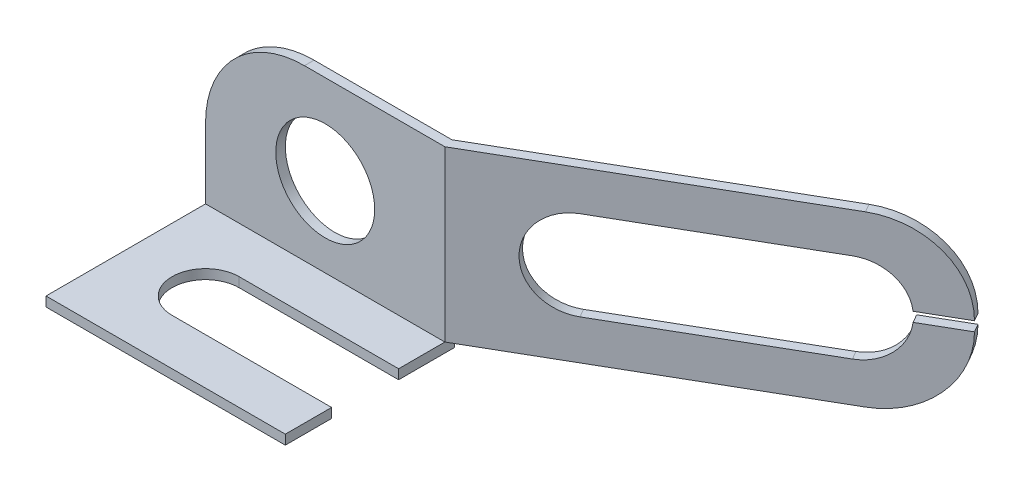
SolidWorks part; units mm, degrees
ref_plane "Front Plane" through (0, 0, 0) normal (0, 0, 1) x (1, 0, 0)
ref_plane "Top Plane" through (0, 0, 0) normal (0, 1, 0) x (1, 0, 0)
ref_plane "Right Plane" through (0, 0, 0) normal (1, 0, 0) x (0, 0, -1)
sketch "Sketch1" plane through (0, 0, 0) normal (0, 0, 1) x (1, 0, 0)
  line L0 (0, -530) -> (0, -30) construction
  line L5 (-130, 530) -> (750, 530)
  line L6 (-750, -90) -> (-750, -530)
  line L7 (-750, -530) -> (750, -530)
  line L12 (750, 530) -> (750, -530)
  line L13 (-750, 530) -> (750, -530) construction
  line L14 (-750, -530) -> (750, 530) construction
  line L16 (-750, -530) -> (750, -530)
  line L17 (-750, -530) -> (-750, -590)
  line L18 (-750, -590) -> (750, -590)
  line L19 (750, -530) -> (750, -590)
  arc A3 (-130, 530) -> (-750, -90) centre (-130, -90) ccw
  circle A4 centre (0, -30) radius 310
  point P0 (0, 0)
  point P13 (0, 0)
  dimension "D3" = 620
  dimension "D4" = 500
  dimension "D5" = 620
  dimension "D1" = 1060
  dimension "D2" = 1500
  dimension "D6" = 60
extrude "Boss-Extrude1" add sketch "Sketch1" along normal blind 1000 contours L17 L16 L19 L18
extrude "Boss-Extrude2" add sketch "Sketch1<6>" against normal blind 60 separate body contours L5 A3 L6 L7 L12 A4 region at (310, 511.6326, 0)
sketch "Sketch1<6>" plane through (0, 0, 0) normal (0, 0, 1) x (1, 0, 0) same geometry as "Sketch1"
sketch "Sketch4" plane through (0, -530, 0) normal (0, -1, 0) x (1, 0, 0)
  line L4 (750, 0) -> (-750, 0)
  line L5 (-750, 0) -> (-750, -60)
  line L6 (-750, -60) -> (750, -60)
  line L7 (750, -60) -> (750, 0)
  line L8 (750, 0) -> (-750, 0)
  line L9 (-750, 0) -> (-750, -60)
  line L10 (-750, -60) -> (750, -60)
  line L11 (750, -60) -> (750, 0)
  dimension "D1" = 0
extrude "Boss-Extrude3" add sketch "Sketch4" along normal blind 60
sketch "Sketch5" plane through (0, -530, 0) normal (0, 1, 0) x (1, 0, 0)
  line L0 (750, -1000) -> (750, -500) construction
  line L1 (750, -1000) -> (750, 0) construction
  line L2 (750, -500) -> (-250, -500) construction
  line L3 (-250, -710) -> (750, -710)
  line L4 (-250, -290) -> (750, -290)
  line L5 (750, -710) -> (750, -290)
  arc A0 (-250, -290) -> (-250, -710) centre (-250, -500) ccw
  dimension "D2" = 420
  dimension "D1" = 1000
extrude "Cut-Extrude2" cut sketch "Sketch5" against normal blind 60
ref_axis "Axis1" through (750, -530, 0) along (0, 1, 0)
ref_plane "Plane1" through (187.5, 0, 324.7595) normal (-0.5, 0, -0.866) x (0, 1, 0)
sketch "Sketch6" plane through (187.5, 0, 324.7595) normal (-0.5, 0, -0.866) x (0, 1, 0)
  line L0 (0, 649.5191) -> (0, 1269.5191) construction
  line L1 (530, 649.5191) -> (-530, 649.5191)
  line L2 (530, 649.5191) -> (530, 2579.5191)
  line L3 (30, 3079.5191) -> (-30, 3079.5191)
  line L4 (-530, 649.5191) -> (-530, 2579.5191)
  line L5 (0, 1269.5191) -> (0, 2519.5191) construction
  line L6 (280, 1269.5191) -> (280, 2519.5191)
  line L7 (-280, 1269.5191) -> (-280, 2519.5191)
  line L8 (30, 3079.5191) -> (30, 2797.9073)
  line L9 (-30, 3079.5191) -> (-30, 2797.9073)
  arc A0 (530, 2579.5191) -> (30, 3079.5191) centre (30, 2579.5191) ccw
  arc A1 (-30, 3079.5191) -> (-530, 2579.5191) centre (-30, 2579.5191) ccw
  arc A2 (-280, 1269.5191) -> (280, 1269.5191) centre (0, 1269.5191) ccw
  arc A3 (280, 2519.5191) -> (30, 2797.9073) centre (0, 2519.5191) ccw
  arc A4 (-30, 2797.9073) -> (-280, 2519.5191) centre (0, 2519.5191) ccw
  point P7 (530, 3079.5191)
  point P10 (-530, 3079.5191)
  dimension "D3" = 500
  dimension "D5" = 560
  dimension "D7" = 560
  dimension "D1" = 2430
  dimension "D2" = 1060
  dimension "D4" = 620
  dimension "D6" = 1250
  dimension "D8" = 1250
  dimension "D10" = 280
extrude "Boss-Extrude4" add sketch "Sketch6" along normal blind 60 contours A4 L9 A1 L4 L1 L2 A0 L8 A3 L6 A2 L7 region at (772.9595, 0, -13.2557)
sketch "Sketch8" plane through (0, -530, 0) normal (0, -1, 0) x (1, 0, 0)
  line L5 (2421.429, -965) -> (750, 0)
  line L6 (750, 0) -> (750, -60)
  line L7 (750, -60) -> (733.923, -60)
  line L8 (733.923, -60) -> (2391.429, -1016.9615)
  line L9 (2391.429, -1016.9615) -> (2421.429, -965)
  line L10 (2421.429, -965) -> (750, 0)
  line L11 (750, 0) -> (750, -60)
  line L12 (750, -60) -> (733.923, -60)
  line L13 (733.923, -60) -> (2391.429, -1016.9615)
  line L14 (2391.429, -1016.9615) -> (2421.429, -965)
  dimension "D1" = 0
